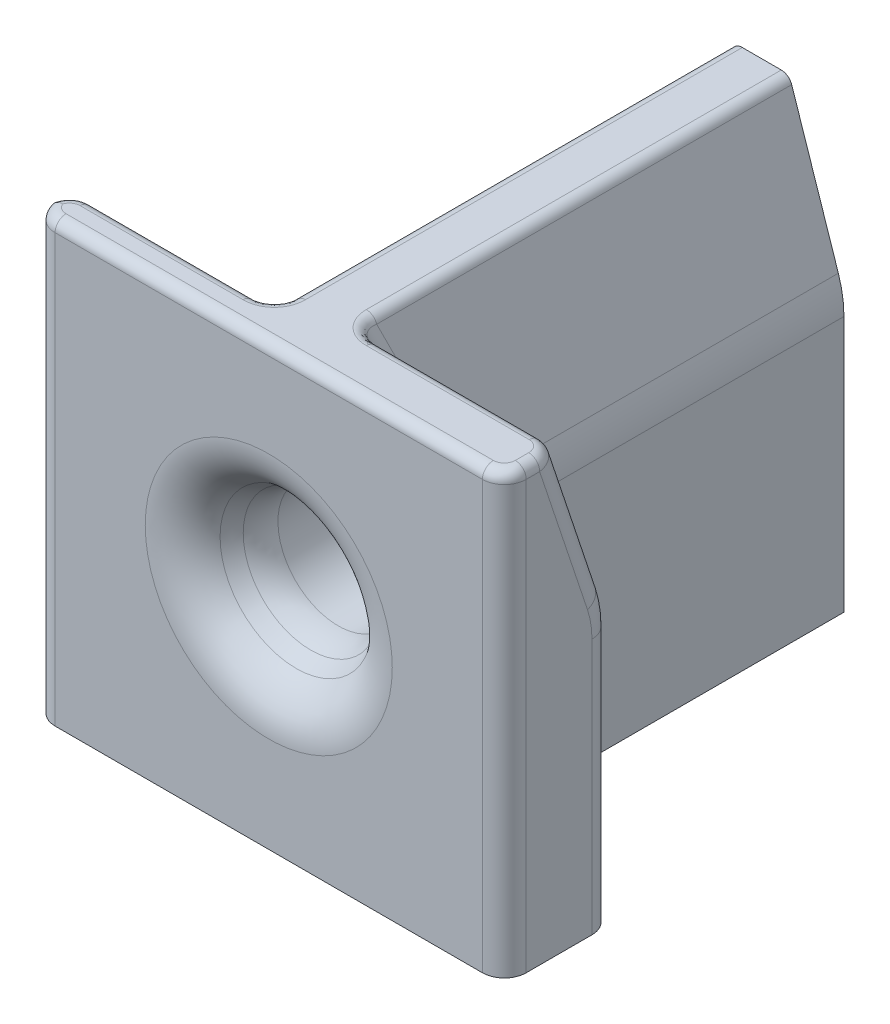
SolidWorks part; units mm, degrees
material "ABS"
ref_plane "Front" through (0, 0, 0) normal (0, 0, 1) x (1, 0, 0)
ref_plane "Top" through (0, 0, 0) normal (0, 1, 0) x (1, 0, 0)
ref_plane "Right" through (0, 0, 0) normal (1, 0, 0) x (0, 0, -1)
sketch "Esquisse1" plane through (0, 0, 0) normal (0, 1, 0) x (1, 0, 0)
  line L0 (-7.5, 0) -> (7.5, 0)
  line L1 (7.5, 0) -> (7.5, -35)
  line L2 (7.5, -35) -> (21.5, -35)
  line L3 (21.5, -35) -> (21.5, -45)
  line L4 (21.5, -45) -> (-21.5, -45)
  line L5 (-21.5, -45) -> (-21.5, -37)
  line L6 (-21.5, -37) -> (-7.5, -37)
  line L7 (-7.5, -37) -> (-7.5, 0)
  dimension "D1" = 37
  dimension "D2" = 15
  dimension "D3" = 14
  dimension "D4" = 10
  dimension "D5" = 35
  dimension "D6" = 14
extrude "Boss.-Extru.1" add sketch "Esquisse1" along normal mid plane 40
chamfer "Chanfrein1" distance 15 distance2 5 4 edges at (-14.5, 20, 37) (-7.5, 20, 18.5) (14.5, 20, 35) (7.5, 20, 17.5) first distance on face at (-14.5, 0, 37) first distance on face at (-7.5, 0, 18.5) first distance on face at (14.5, 0, 35) first distance on face at (7.5, 0, 17.5)
fillet "Congé1" radius 10 4 edges at (14.5, 5, 35) (7.5, 5, 17.5) (-14.5, 5, 37) (-7.5, 5, 18.5)
fillet "Congé2" radius 2 14 edges at (-4.7434, 13.2698, 39.7566) (-7.3709, 4.979, 37.1291) (4.7434, 13.2698, 37.7566) (7.3709, 4.979, 35.1291) (21.5, 13.2698, 37.7566) (21.5, 4.979, 35.1291) (-21.5, 13.2698, 39.7566) (-21.5, 4.979, 37.1291) (21.5, 0, 45) (-21.5, 0, 45) (-7.5, -8.3114, 37) (7.5, -8.3114, 35) (21.5, -8.3114, 35) (-21.5, -8.3114, 37)
fillet "Congé3" radius 1 12 edges at (-20.7085, 20, 42.4284) (-11.9487, 20, 42) (-3.0447, 20, 41.4553) (-20.7085, 20, 44.5936) (0, 20, 45) (20.9142, 20, 44.4142) (21.5, 20, 42.5541) (20.9142, 20, 40.6175) (11.9487, 20, 40) (3.0447, 20, 39.4553) (-2.5, 20, 20.0513) (2.5, 20, 19.0513)
sketch "Esquisse3" plane through (0, 0, 0) normal (1, 0, 0) x (0, 0, -1)
  line L0 (-45, -20) -> (-45, 19) construction
  line L1 (0, 0) -> (-45, 0)
  line L2 (0, 0) -> (0, 2)
  line L3 (-6.9368, 5.5) -> (-45, 5.5)
  line L4 (-45, 0) -> (-45, 5.5)
  line L5 (-45, 0) -> (-50.5, 0) construction
  line L8 (0, 2) -> (-4, 2)
  line L9 (-6.9368, 5.5) -> (-4, 2)
  dimension "D1" = 4
  dimension "D2" = 11
  dimension "D3" = 50
  dimension "D4" = 4
revolve "Enlèvement de matière-Révolution1" cut sketch "Esquisse3" angle 360 about L5
chamfer "Chanfrein2" distance 5 angle 30 1 edges at (0, 5.5, 45) first distance on face at (0, 5.5, 45)
fillet "Congé4" radius 5 2 edges at (0, 5.5, 40) (-8.3868, 0, 45)
